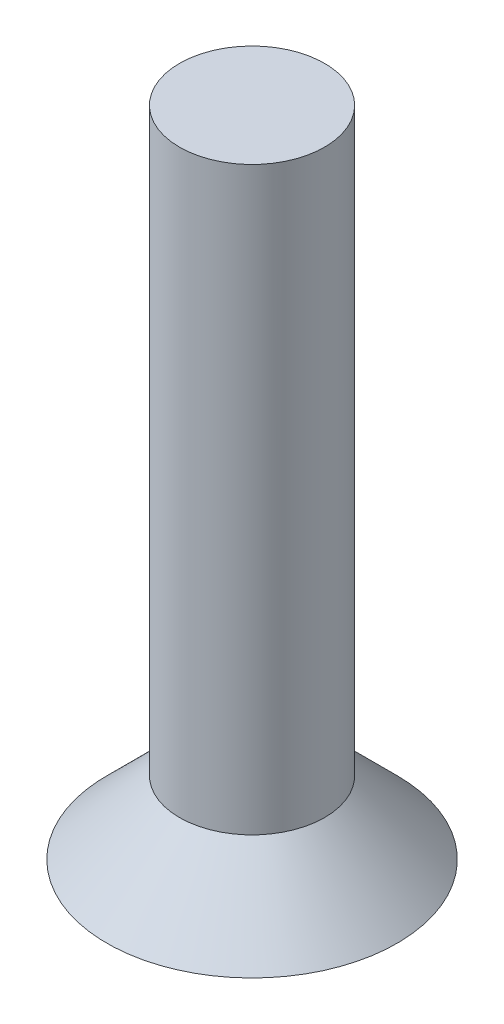
SolidWorks part; units mm, degrees
material "AISI 316 Stainless Steel Sheet (SS)"
ref_plane "Front Plane" through (0, 0, 0) normal (0, 0, 1) x (1, 0, 0)
ref_plane "Top Plane" through (0, 0, 0) normal (0, 1, 0) x (1, 0, 0)
ref_plane "Right Plane" through (0, 0, 0) normal (1, 0, 0) x (0, 0, -1)
sketch "Sketch1" plane through (0, 0, 0) normal (0, 1, 0) x (1, 0, 0)
  circle A0 centre (0, 0) radius 1
  dimension "D1" = 2
extrude "Boss-Extrude1" add sketch "Sketch1" along normal blind 8
sketch "Sketch2" plane through (0, 0, 0) normal (0, -1, 0) x (1, 0, 0)
  circle A0 centre (0, 0) radius 2
  dimension "D1" = 4
extrude "Boss-Extrude2" add sketch "Sketch2" along normal blind 1
chamfer "Chamfer1" distance 1 angle 45 1 edges at (0, 0, -2)
